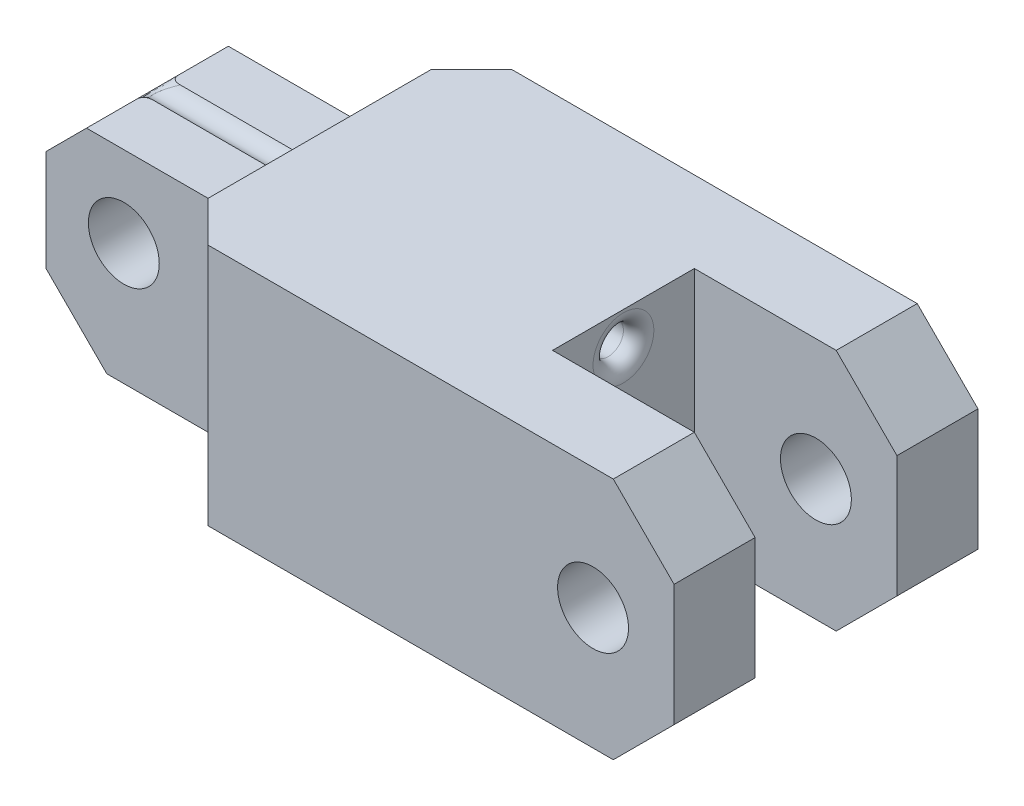
SolidWorks part; units mm, degrees
ref_plane "Спереди" through (0, 0, 0) normal (0, 0, 1) x (1, 0, 0)
ref_plane "Сверху" through (0, 0, 0) normal (0, 1, 0) x (1, 0, 0)
ref_plane "Справа" through (0, 0, 0) normal (1, 0, 0) x (0, 0, -1)
sketch "Эскиз2" plane through (0, 0, 0) normal (1, 0, 0) x (0, 0, -1)
  line L1 (-7.5, 6) -> (7.5, 6)
  line L2 (-7.5, 6) -> (-7.5, -6)
  line L3 (-7.5, -6) -> (7.5, -6)
  line L4 (7.5, 6) -> (7.5, -6)
  line L5 (-7.5, 6) -> (7.5, -6) construction
  line L6 (-7.5, -6) -> (7.5, 6) construction
  point P0 (0, 0)
extrude "Вытянуть1" add sketch "Эскиз2" along normal blind 35
sketch "Эскиз3" plane through (0, 6, 0) normal (0, 1, 0) x (1, 0, 0)
  line L0 (0, 0) -> (-9.2006, 0) construction
  line L1 (10, -9.9613) -> (10, -3.5)
  line L2 (-3.345, 9.9613) -> (10, 9.9613)
  line L3 (-3.345, 9.9613) -> (-3.345, 3.5)
  line L4 (-3.345, 3.5) -> (10, 3.5)
  line L5 (10, 9.9613) -> (10, 3.5)
  line L6 (-3.345, -9.9613) -> (10, -9.9613)
  line L7 (-3.345, -3.5) -> (10, -3.5)
  line L8 (-3.345, -9.9613) -> (-3.345, -3.5)
  line L9 (0, 7.5) -> (0, -7.5) construction
  dimension "D1" = 3.5
  dimension "D2" = 10
extrude "Вырез-Вытянуть1" cut sketch "Эскиз3" against normal through all
sketch "Эскиз4" plane through (0, 0, 3.5) normal (0, 0, 1) x (1, 0, 0)
  circle A0 centre (3.8399, 0) radius 1.75
extrude "Вытянуть2" cut sketch "Эскиз4" against normal through all
sketch "Эскиз5" plane through (0, 6, 0) normal (0, 1, 0) x (1, 0, 0)
  line L0 (40, 0) -> (51.6105, 0) construction
  line L2 (35, 7.5) -> (35, -7.5) construction
  line L3 (25, 3.5) -> (45.3677, 3.5)
  line L4 (25, 3.5) -> (25, -3.5)
  line L5 (25, -3.5) -> (45.3677, -3.5)
  line L6 (45.3677, 3.5) -> (45.3677, -3.5)
  line L7 (25, 3.5) -> (45.3677, -3.5) construction
  line L8 (25, -3.5) -> (45.3677, 3.5) construction
  point P1 (35.1838, 0)
  dimension "D1" = 10
extrude "Вырез-Вытянуть2" cut sketch "Эскиз5" against normal through all
chamfer "Фаска4" distance 3 angle 45 4 edges at (35, -6, -5.5) (35, -6, 5.5) (35, 6, -5.5) (35, 6, 5.5)
sketch "Эскиз7" plane through (25, 0, 0) normal (1, 0, 0) x (0, 0, -1)
  line L0 (0, 6) -> (0, 3.9395) construction
  circle A0 centre (0, 4.3577) radius 0.75
extrude "Вытянуть3" cut sketch "Эскиз7" against normal through all
chamfer "Фаска5" distance 3 angle 45 1 edges at (0, -6, 0)
sketch "Эскиз8" plane through (0, 0, 0) normal (-1, 0, 0) x (0, 0, 1)
  line L0 (0, 6) -> (0, 2.0994) construction
  line L2 (-3.5, 6) -> (-7.5, 6) construction
  line L3 (-3.9395, 7.8642) -> (3.9729, 7.8642)
  line L4 (-3.9395, 7.8642) -> (-3.9395, 4)
  line L5 (-3.9395, 4) -> (3.9729, 4)
  line L6 (3.9729, 7.8642) -> (3.9729, 4)
  dimension "D1" = 2
extrude "Вытянуть4" cut sketch "Эскиз8" against normal blind 10
chamfer "Фаска6" distance 2 angle 45 2 edges at (0, 4, 2.0796) (0, 4, -2.0796)
fillet "Скругление1" radius 0.75 2 edges at (10, 5.1077, 0) (25, 4.3577, -0.75)
sketch "Эскиз9" plane through (0, 0, 7.5) normal (0, 0, 1) x (1, 0, 0)
  line L0 (30.3754, 0) -> (53.7127, 0) construction
  line L2 (35, 3) -> (35, -3) construction
  circle A0 centre (31, 0) radius 1.75
  dimension "D1" = 4
extrude "Вырез-Вытянуть3" cut sketch "Эскиз9" against normal through all
fillet "Скругление2" radius 0.5 1 edges at (1.6077, 3.6077, 0)
chamfer "Фаска8" distance 2 angle 45 2 edges at (10, 0, -7.5) (10, 0, 7.5)
